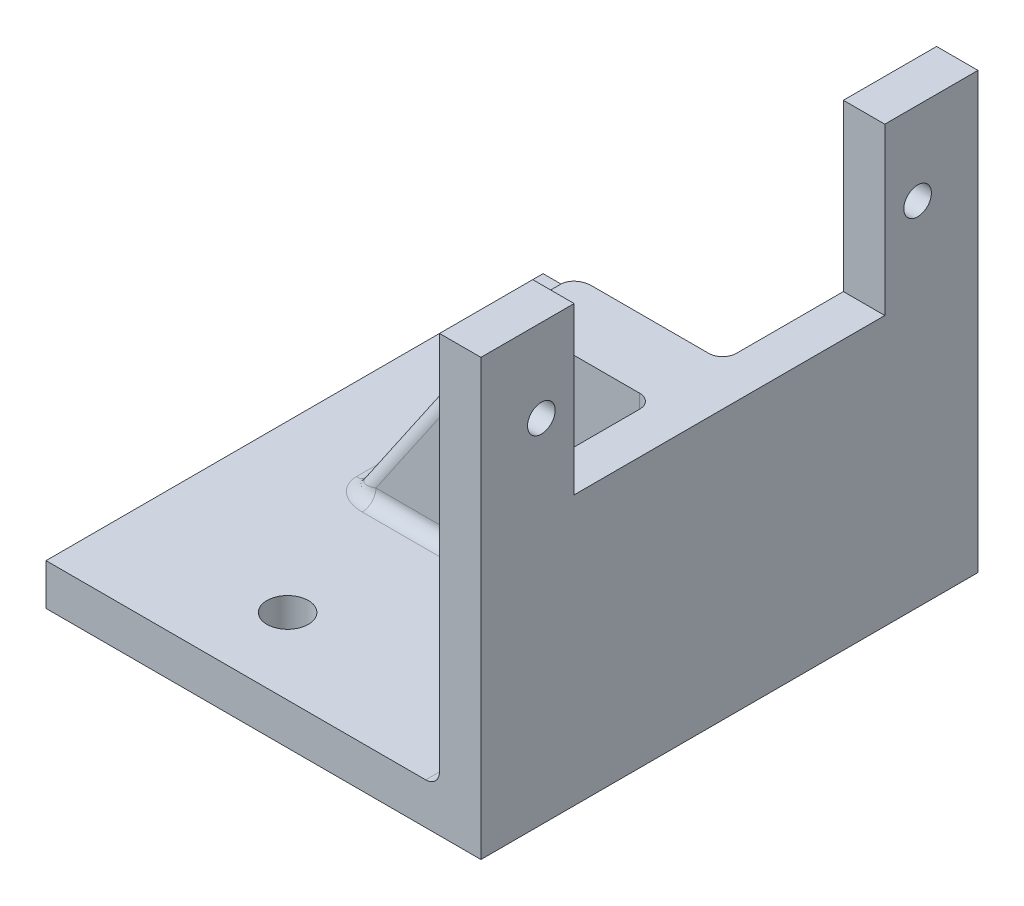
SolidWorks part; units mm, degrees
ref_plane "Front Plane" through (0, 0, 0) normal (0, 0, 1) x (1, 0, 0)
ref_plane "Top Plane" through (0, 0, 0) normal (0, 1, 0) x (1, 0, 0)
ref_plane "Right Plane" through (0, 0, 0) normal (1, 0, 0) x (0, 0, -1)
sketch "Sketch1" plane through (0, 0, 0) normal (0, 0, 1) x (1, 0, 0)
  line L0 (0, 0) -> (-30, 0)
  line L2 (0, 0) -> (0, 30)
  dimension "D1" = 30
  dimension "D2" = 30
extrude "Extrude-Thin1" add sketch "Sketch1" along normal mid plane 36 thin thin type mid plane wall 3
sketch "Sketch2" plane through (0, 30, 0) normal (0, 1, 0) x (1, 0, 0)
  line L0 (1.5, -18) -> (1.5, 18) construction
  line L1 (-1.5, -11.25) -> (1.5, -11.25)
  line L2 (-1.5, -11.25) -> (-1.5, 11.25)
  line L3 (-1.5, 11.25) -> (1.5, 11.25)
  line L4 (1.5, -11.25) -> (1.5, 11.25)
  line L5 (-1.5, -11.25) -> (1.5, 11.25) construction
  line L6 (-1.5, 11.25) -> (1.5, -11.25) construction
  point P0 (0, 0)
  dimension "D1" = 22.5
extrude "Cut-Extrude1" cut sketch "Sketch2" against normal blind 12
sketch "Sketch3" plane through (1.5, 0, 0) normal (1, 0, 0) x (0, 0, -1)
  line L0 (-13.625, 24) -> (13.625, 24) construction
  line L3 (-13.625, 24) -> (-18, 24) construction
  line L4 (-18, -1.5) -> (-18, 30) construction
  line L5 (13.625, 24) -> (18, 24) construction
  line L6 (18, -1.5) -> (18, 30) construction
  circle A0 centre (-13.625, 24) radius 1
  circle A1 centre (13.625, 24) radius 1
  dimension "D1" = 27.25
  dimension "D2" = 2
  dimension "D3" = 2
extrude "Cut-Extrude2" cut sketch "Sketch3" against normal through all
sketch "Sketch7" plane through (0, 0, 0) normal (0, 0, 1) x (1, 0, 0)
  line L4 (-1.5, 1.5) -> (-23.5, 1.5)
  line L5 (-1.5, 1.5) -> (-1.5, 18)
  line L6 (-1.5, 18) -> (-12.1973, 18)
  line L9 (-12.1973, 18) -> (-23.5, 1.5)
  dimension "D1" = 16.5
  dimension "D2" = 22
  dimension "D3" = 20
extrude "Boss-Extrude2" add sketch "Sketch7" along normal mid plane 5
fillet "Fillet3" radius 1 8 edges at (-12.5, 1.5, -2.5) (-1.5, 1.5, -10.25) (-17.8487, 9.75, -2.5) (-17.8487, 9.75, 2.5) (-23.5, 1.5, 0) (-12.5, 1.5, 2.5) (-1.5, 9.75, 2.5) (-1.5, 1.5, 10.25)
fillet "Fillet4" radius 1 2 edges at (-1.7929, 1.7929, -2.7929) (-1.5, 10.25, -2.5)
sketch "Sketch8" plane through (0, 1.5, 0) normal (0, 1, 0) x (1, 0, 0)
  line L0 (0, 0) -> (-44.1041, 0) construction
  line L1 (-30, -18) -> (-30, 18) construction
  circle A0 centre (-18, 12.5) radius 1.5
  circle A1 centre (-18, -12.5) radius 1.5
  dimension "D1" = 25
  dimension "D2" = 3
  dimension "D3" = 12
extrude "Cut-Extrude3" cut sketch "Sketch8" against normal through all
